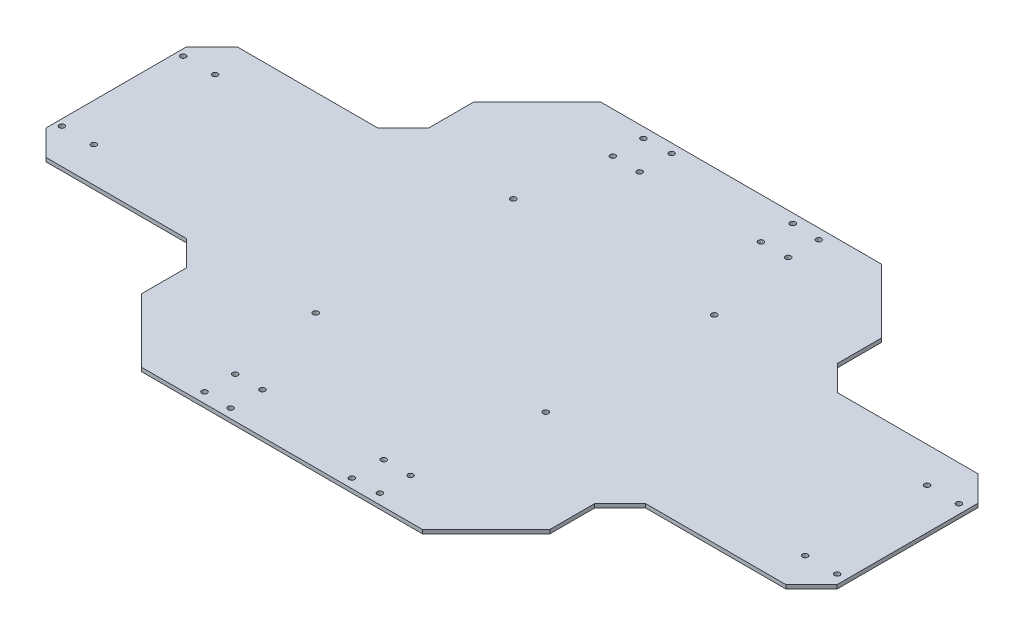
SolidWorks part; units mm, degrees
ref_plane "前视基准面" through (0, 0, 0) normal (0, 0, 1) x (1, 0, 0)
ref_plane "上视基准面" through (0, 0, 0) normal (0, 1, 0) x (1, 0, 0)
ref_plane "右视基准面" through (0, 0, 0) normal (1, 0, 0) x (0, 0, -1)
sketch "草图1" plane through (0, 0, 0) normal (0, 1, 0) x (1, 0, 0)
  line L0 (-310, 75) -> (310, -75) construction
  line L1 (-260, 200) -> (260, 200) construction
  line L2 (-260, 200) -> (-260, -200) construction
  line L3 (-260, -200) -> (260, -200) construction
  line L4 (260, 200) -> (260, -200) construction
  line L5 (310, 75.5001) -> (-310, -75) construction
  line L6 (-160, 200) -> (160, -200) construction
  line L7 (-310, -75) -> (-160, -75)
  line L8 (-310, -75) -> (-310, 75)
  line L9 (-310, 75) -> (-160, 75)
  line L10 (310, -75) -> (310, 75.5001)
  line L11 (160, 200) -> (-160, -200) construction
  line L13 (-160, -200) -> (160, -200)
  line L14 (-160, -200) -> (-160, -75)
  line L15 (-160, 200) -> (160, 200)
  line L16 (160, -200) -> (160, -75)
  line L19 (-160, 75) -> (-160, 200)
  line L22 (160, 75.5001) -> (310, 75.5001)
  line L25 (160, 75.5001) -> (160, 200)
  line L28 (160, -75) -> (310, -75)
  point P0 (0, 0)
  point P6 (-0.5159, 0.1248)
  point P11 (0, 0)
  dimension "D1" = 520
  dimension "D2" = 400
  dimension "D3" = 50
  dimension "D4" = 125
  dimension "D5" = 100
extrude "凸台-拉伸1" add sketch "草图1" along normal blind 3
chamfer "倒角1" distance 20 angle 45 8 edges at (-160, 1.5, -75) (-310, 1.5, -75) (-310, 1.5, 75) (-160, 1.5, 75) (160, 1.5, 75) (160, 1.5, -75.5001) (310, 1.5, 75) (310, 1.5, -75.5001)
sketch "草图2" plane through (0, 3, 0) normal (0, 1, 0) x (1, 0, 0)
  line L0 (-160, 200) -> (-160, 95) construction
  line L1 (-160, 180) -> (160, 180)
  line L2 (-160, 180) -> (-160, 200)
  line L3 (-160, 200) -> (160, 200)
  line L4 (160, 180) -> (160, 200)
  line L6 (160, -200) -> (-160, -200)
  line L7 (160, -200) -> (160, -180)
  line L8 (160, -180) -> (-160, -180)
  line L9 (-160, -200) -> (-160, -180)
  dimension "D1" = 20
  dimension "D2" = 20
extrude "切除-拉伸1" cut sketch "草图2" against normal blind 5
chamfer "倒角2" distance 50 angle 45 4 edges at (-160, 1.5, -180) (-160, 1.5, 180) (160, 1.5, -180) (160, 1.5, 180)
sketch "草图3" plane through (0, 3, 0) normal (0, 1, 0) x (1, 0, 0)
  line L0 (0, 0) -> (144.0598, 0) construction
  circle A0 centre (-305, 47.5) radius 2.1
  circle A1 centre (-280, 47.5) radius 2.1
  circle A2 centre (-47.5, 172.8263) radius 2.1
  circle A3 centre (-47.5, 147.8263) radius 2.1
  circle A4 centre (47.5, 172.8263) radius 2.1
  circle A5 centre (47.5, 147.8263) radius 2.1
  circle A6 centre (277.8263, 47.7501) radius 2.1
  circle A7 centre (302.8263, 47.7501) radius 2.1
  circle A8 centre (-68.75, 172) radius 2.1
  circle A9 centre (-68.75, 148) radius 2.1
  circle A10 centre (68.75, 172) radius 2.1
  circle A11 centre (68.75, 148) radius 2.1
  circle A12 centre (68.75, -148) radius 2.1
  circle A13 centre (68.75, -172) radius 2.1
  circle A14 centre (-68.75, -148) radius 2.1
  circle A15 centre (-68.75, -172) radius 2.1
  circle A16 centre (302.8263, -47.7501) radius 2.1
  circle A17 centre (277.8263, -47.7501) radius 2.1
  circle A18 centre (47.5, -147.8263) radius 2.1
  circle A19 centre (47.5, -172.8263) radius 2.1
  circle A20 centre (-47.5, -147.8263) radius 2.1
  circle A21 centre (-47.5, -172.8263) radius 2.1
  circle A22 centre (-280, -47.5) radius 2.1
  circle A23 centre (-305, -47.5) radius 2.1
  dimension "D1" = 4.2
  dimension "D2" = 4.2
  dimension "D3" = 4.2
  dimension "D4" = 4.2
  dimension "D5" = 4.2
  dimension "D6" = 4.2
  dimension "D7" = 4.2
  dimension "D8" = 4.2
extrude "切除-拉伸2" cut sketch "草图3" against normal blind 80
sketch "草图4" plane through (0, 0, 0) normal (0, -1, 0) x (1, 0, 0)
  circle A0 centre (-78.74, 74.91) radius 2.15
  arc A1 (-76.765, 74.91) -> (-80.715, 74.91) centre (-78.74, 74.91) ccw construction
  circle A2 centre (-78.74, -80.01) radius 2.15
  circle A3 centre (78.74, -80.01) radius 2.15
  circle A4 centre (78.74, 52.07) radius 2.15
  dimension "D1" = 4.3
  dimension "D2" = 4.3
  dimension "D3" = 4.3
  dimension "D4" = 4.3
extrude "切除-拉伸3" cut sketch "草图4" against normal blind 10
